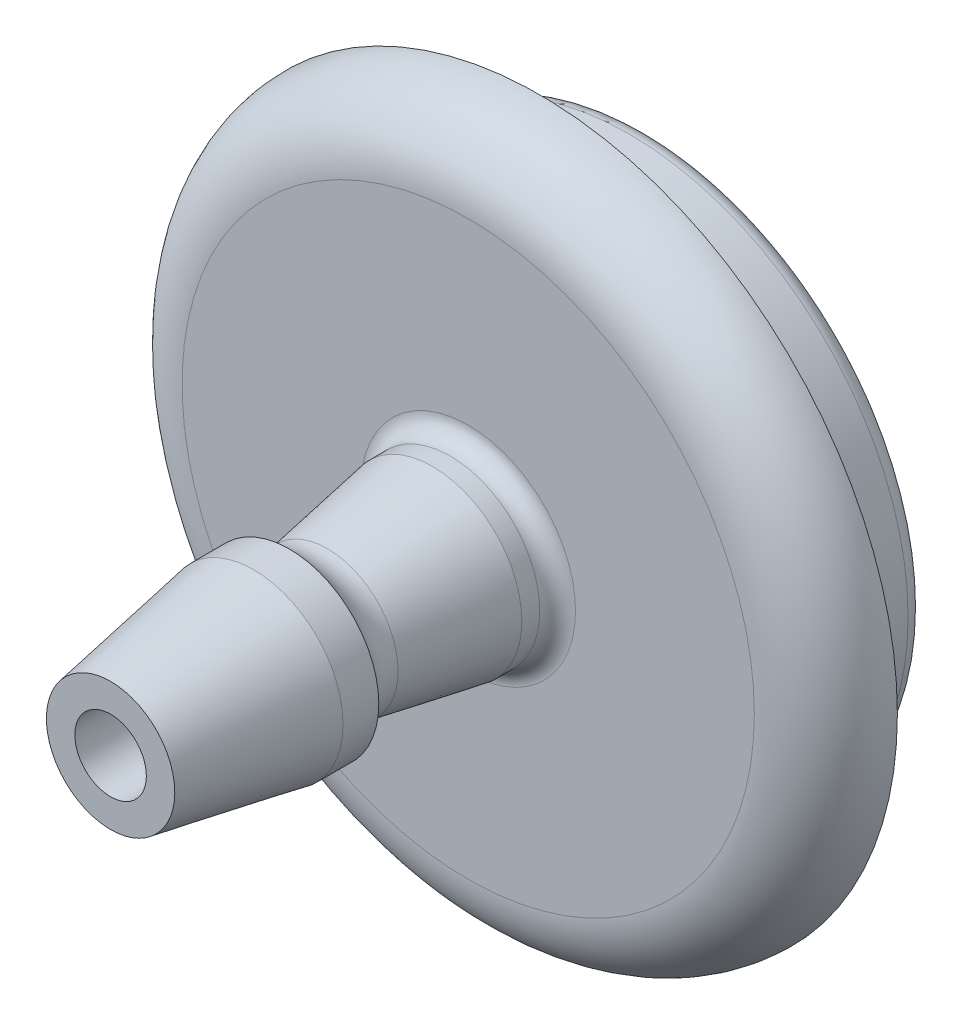
SolidWorks part; units mm, degrees
ref_plane "Front Plane" through (0, 0, 0) normal (0, 0, 1) x (1, 0, 0)
ref_plane "Top Plane" through (0, 0, 0) normal (0, 1, 0) x (1, 0, 0)
ref_plane "Right Plane" through (0, 0, 0) normal (1, 0, 0) x (0, 0, -1)
sketch "Sketch1" plane through (0, 0, 0) normal (0, 0, 1) x (1, 0, 0)
  circle A0 centre (0, 0) radius 2.5
  circle A1 centre (0, 0) radius 1
extrude "Boss-Extrude1" add sketch "Sketch1" along normal blind 5
chamfer "Chamfer2" distance 4 angle 10 1 edges at (2.5, 0, 5) first distance on face at (2.5, 0, 5)
ref_plane "Plane1" [suppressed] through (0, 0, 5) normal (0, 0, 1) x (1, 0, 0)
pattern_linear "LPattern2" count 2 spacing 5 along (0, 0, 1) of "Boss-Extrude1", "Chamfer2"
fillet "Fillet1" radius 1 1 edges at (1.7947, 0, 5)
sketch "Sketch2" plane through (0, 0, 0) normal (0, 0, 1) x (1, 0, 0)
  circle A0 centre (0, 0) radius 10
extrude "Boss-Extrude2" add sketch "Sketch2" against normal blind 2
sketch "Sketch4" plane through (0, 0, 0) normal (0, 0, 1) x (1, 0, 0)
  circle A0 centre (0, 0) radius 1
extrude "Cut-Extrude2" cut sketch "Sketch4" against normal blind 15
fillet "Fillet3" radius 2 1 edges at (1, 0, -2)
sketch "Sketch5" plane through (0, 0, 0) normal (0, 0, 1) x (1, 0, 0)
  circle A0 centre (0, 0) radius 7.8
  circle A1 centre (0, 0) radius 6
extrude "Boss-Extrude3" add sketch "Sketch5" against normal blind 5
fillet "Fillet4" radius 2 1 edges at (10, 0, 0)
fillet "Fillet5" radius 0.5 1 edges at (2.5, 0, 0)
fillet "Fillet6" radius 0.5 1 edges at (7.8, 0, -5)
